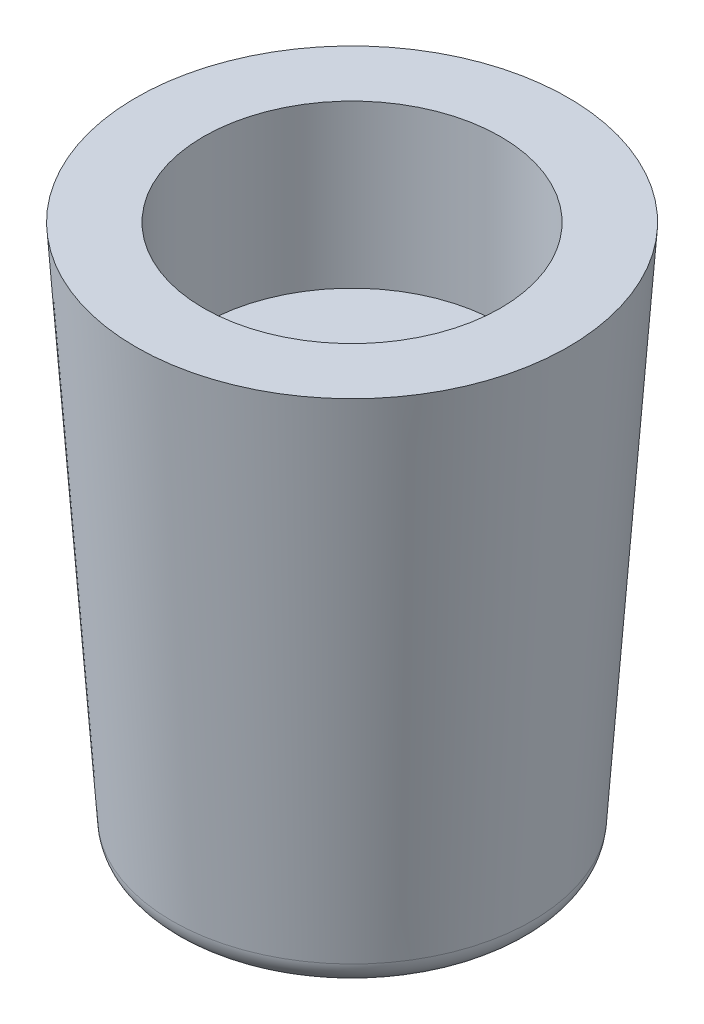
SolidWorks part; units mm, degrees
ref_plane "Front Plane" through (0, 0, 0) normal (0, 0, 1) x (1, 0, 0)
ref_plane "Top Plane" through (0, 0, 0) normal (0, 1, 0) x (1, 0, 0)
ref_plane "Right Plane" through (0, 0, 0) normal (1, 0, 0) x (0, 0, -1)
sketch "Sketch1" plane through (0, 0, 0) normal (0, 1, 0) x (1, 0, 0)
  circle A0 centre (0, 0) radius 4
  dimension "D1" = 8
extrude "Boss-Extrude1" add sketch "Sketch1" against normal blind 10 draft 4
sketch "Sketch2" plane through (0, 0, 0) normal (0, 1, 0) x (1, 0, 0)
  circle A0 centre (0, 0) radius 2.75
  dimension "D1" = 5.5
extrude "Boss-Extrude2" add sketch "Sketch2" against normal blind 3
extrude "Cut-Extrude1" cut sketch "Sketch2<3>" against normal blind 3 and the other way through all
sketch "Sketch2<3>" plane through (0, 0, 0) normal (0, 1, 0) x (1, 0, 0) same geometry as "Sketch2"
fillet "Fillet1" radius 0.5 1 edges at (0, -10, 3.3007)
